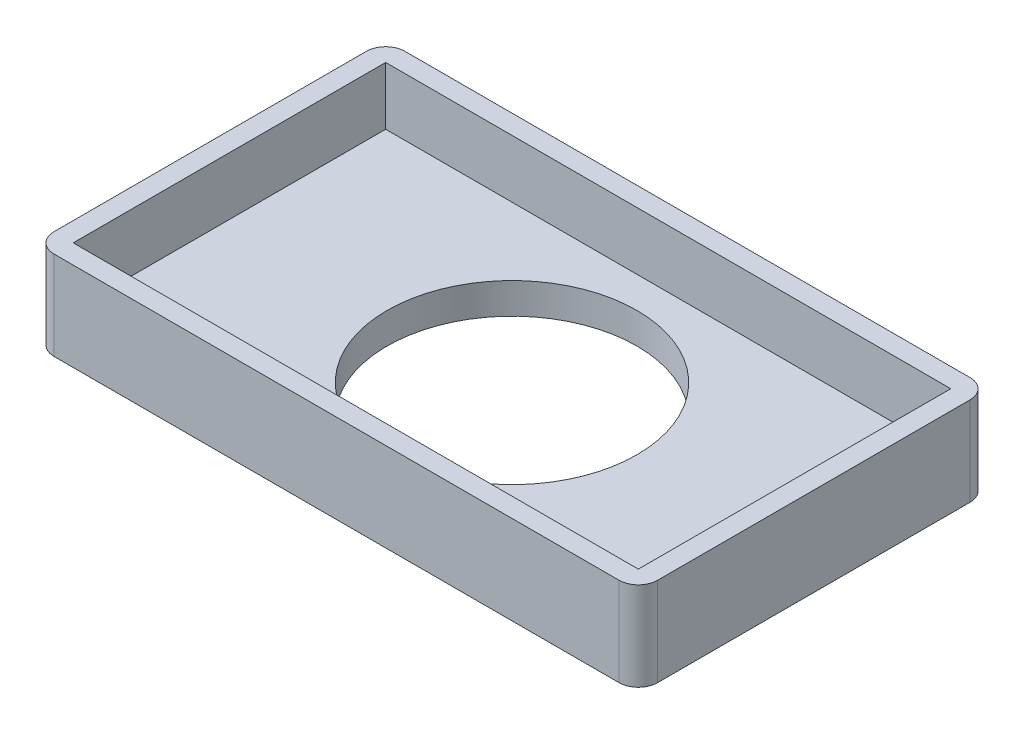
SolidWorks part; units mm, degrees
ref_plane "Front Plane" through (0, 0, 0) normal (0, 0, 1) x (1, 0, 0)
ref_plane "Top Plane" through (0, 0, 0) normal (0, 1, 0) x (1, 0, 0)
ref_plane "Right Plane" through (0, 0, 0) normal (1, 0, 0) x (0, 0, -1)
sketch "Sketch1" plane through (0, 0, 0) normal (0, 1, 0) x (1, 0, 0)
  line L1 (-78.25, 45.5) -> (78.25, 45.5)
  line L2 (-78.25, 45.5) -> (-78.25, -45.5)
  line L3 (-78.25, -45.5) -> (78.25, -45.5)
  line L4 (78.25, 45.5) -> (78.25, -45.5)
  line L5 (-78.25, 45.5) -> (78.25, -45.5) construction
  line L6 (-78.25, -45.5) -> (78.25, 45.5) construction
  point P0 (0, 0)
  dimension "D1" = 156.5
  dimension "D2" = 91
extrude "Boss-Extrude1" add sketch "Sketch1" along normal blind 8
sketch "Sketch2" plane through (0, 8, 0) normal (0, 1, 0) x (1, 0, 0)
  line L1 (-73.25, 40.5) -> (73.25, 40.5)
  line L2 (-73.25, 40.5) -> (-73.25, -40.5)
  line L3 (-73.25, -40.5) -> (73.25, -40.5)
  line L4 (73.25, 40.5) -> (73.25, -40.5)
  line L5 (-73.25, 40.5) -> (73.25, -40.5) construction
  line L6 (-73.25, -40.5) -> (73.25, 40.5) construction
  line L7 (-78.25, 45.5) -> (78.25, 45.5)
  line L8 (-78.25, 45.5) -> (-78.25, -45.5)
  line L9 (-78.25, -45.5) -> (78.25, -45.5)
  line L10 (78.25, 45.5) -> (78.25, -45.5)
  line L11 (-78.25, 45.5) -> (78.25, -45.5) construction
  line L12 (-78.25, -45.5) -> (78.25, 45.5) construction
  point P0 (0, 0)
  point P6 (0, 0)
  dimension "D1" = 146.5
  dimension "D2" = 81
extrude "Boss-Extrude2" add sketch "Sketch2" along normal blind 15
sketch "Sketch3" plane through (0, 0, 0) normal (0, -1, 0) x (1, 0, 0)
  circle A0 centre (0, 0) radius 32.4
  dimension "D1" = 64.8
extrude "Cut-Extrude1" cut sketch "Sketch3" against normal through all
fillet "Fillet1" radius 5 1 edges at (-78.25, 11.5, 45.5)
fillet "Fillet2" radius 5 3 edges at (78.25, 11.5, 45.5) (78.25, 11.5, -45.5) (-78.25, 11.5, -45.5)
sketch "Sketch4" plane through (0, 23, 0) normal (0, 1, 0) x (1, 0, 0)
  line L1 (-28.25, 40.5) -> (-28.25, 45.5)
  line L2 (73.25, 40.5) -> (-73.25, 40.5) construction
  line L3 (73.25, 45.5) -> (-73.25, 45.5) construction
  line L4 (-28.25, 45.5) -> (-28.25, 40.5)
  line L5 (53.25, 40.5) -> (53.25, 45.5)
  line L6 (53.25, 45.5) -> (53.25, 40.5)
  line L7 (-78.25, 40.5) -> (-78.25, -40.5) construction
  line L8 (78.25, -40.5) -> (78.25, 40.5) construction
  dimension "D1" = 50
  dimension "D2" = 25
sketch "Sketch5" plane through (0, 0, -45.5) normal (0, 0, -1) x (-1, 0, 0)
  line L0 (-53.25, 23) -> (-53.25, 0)
  line L1 (-73.25, 0) -> (73.25, 0) construction
  line L2 (28.25, 23) -> (28.25, 0)
